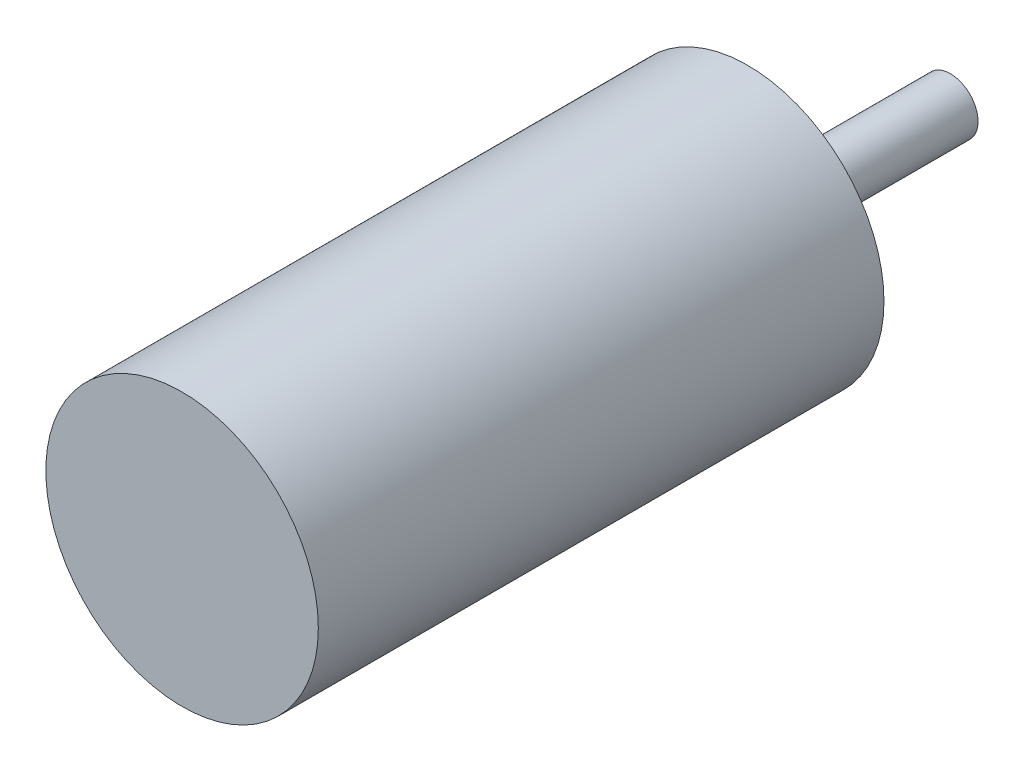
SolidWorks part; units mm, degrees
ref_plane "Front Plane" through (0, 0, 0) normal (0, 0, 1) x (1, 0, 0)
ref_plane "Top Plane" through (0, 0, 0) normal (0, 1, 0) x (1, 0, 0)
ref_plane "Right Plane" through (0, 0, 0) normal (1, 0, 0) x (0, 0, -1)
sketch "Sketch2" plane through (0, 0, 0) normal (0, 0, 1) x (1, 0, 0)
  circle A0 centre (0, 0) radius 19.75
  dimension "D1" = 39.5
extrude "Boss-Extrude1" add sketch "Sketch2" against normal blind 82
sketch "Sketch3" plane through (0, 0, -82) normal (0, 0, -1) x (-1, 0, 0)
  circle A0 centre (0, 0) radius 4
  dimension "D1" = 8
extrude "Boss-Extrude2" add sketch "Sketch3" along normal blind 29.3878
